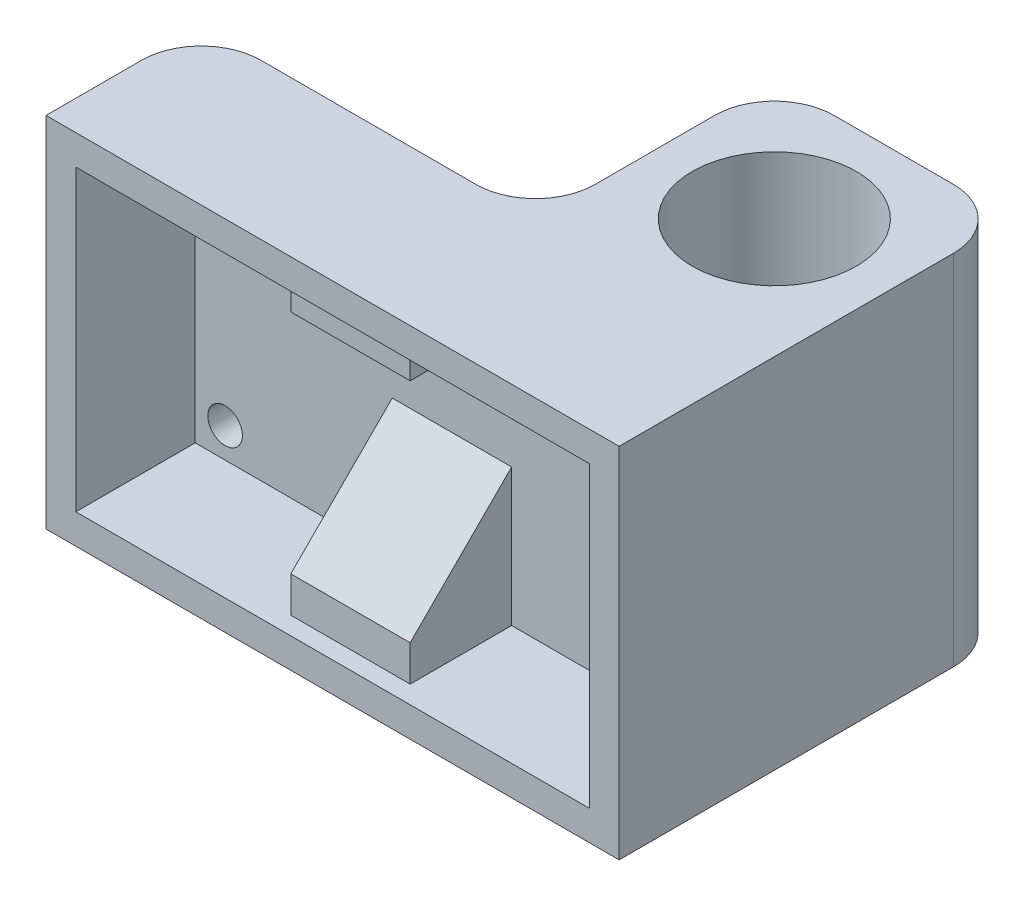
SolidWorks part; units mm, degrees
ref_plane "Front Plane" through (0, 0, 0) normal (0, 0, 1) x (1, 0, 0)
ref_plane "Top Plane" through (0, 0, 0) normal (0, 1, 0) x (1, 0, 0)
ref_plane "Right Plane" through (0, 0, 0) normal (1, 0, 0) x (0, 0, -1)
sketch "Sketch1" plane through (0, 0, 0) normal (0, 0, 1) x (1, 0, 0)
  line L0 (-0.5, 24.5) -> (16, 24.5)
  line L1 (0, 0) -> (42, 0) construction
  line L2 (0, 0) -> (0, 24) construction
  line L3 (0, 24) -> (42, 24) construction
  line L4 (42, 0) -> (42, 24) construction
  line L5 (-3, 27) -> (45, 27)
  line L6 (-3, 27) -> (-3, -3)
  line L7 (-3, -3) -> (45, -3)
  line L8 (45, 27) -> (45, -3)
  line L9 (42.5, 24.5) -> (42.5, -0.5)
  line L10 (-0.5, -0.5) -> (16, -0.5)
  line L11 (-0.5, 24.5) -> (-0.5, -0.5)
  line L12 (26, 24.5) -> (42.5, 24.5)
  line L14 (16, 24.5) -> (16, 21.5)
  line L15 (16, 21.5) -> (26, 21.5)
  line L16 (26, 24.5) -> (26, 21.5)
  line L18 (16, -0.5) -> (16, 2.5)
  line L19 (16, 2.5) -> (26, 2.5)
  line L20 (26, -0.5) -> (26, 2.5)
  line L21 (-0.5, 24.5) -> (42.5, 24.5) construction
  line L22 (26, -0.5) -> (42.5, -0.5)
  line L23 (-0.5, -0.5) -> (42.5, -0.5) construction
  circle A0 centre (2, 22) radius 1.625 construction
  circle A1 centre (2, 2) radius 1.625 construction
  circle A2 centre (40, 22) radius 1.625 construction
  circle A3 centre (40, 2) radius 1.625 construction
  point P29 (21, 27)
  point P30 (21, 21.5)
  point P31 (21, 2.5)
  dimension "D3" = 3.25
  dimension "D1" = 42
  dimension "D2" = 24
  dimension "D4" = 2
  dimension "D5" = 2
  dimension "D6" = 2
  dimension "D7" = 2
  dimension "D8" = 3
  dimension "D9" = 3
  dimension "D10" = 3
  dimension "D11" = 3
  dimension "D13" = 3
  dimension "D14" = 10
  dimension "D12" = 2.5
extrude "Boss-Extrude1" add sketch "Sketch1" along normal blind 10
sketch "Sketch2" plane through (0, 0, 10) normal (0, 0, 1) x (1, 0, 0)
  line L1 (16, -0.5) -> (26, -0.5)
  line L2 (16, -0.5) -> (16, 2.5)
  line L3 (16, 2.5) -> (26, 2.5)
  line L4 (26, -0.5) -> (26, 2.5)
  line L5 (16, 21.5) -> (26, 21.5)
  line L6 (16, 21.5) -> (16, 24.5)
  line L7 (16, 24.5) -> (26, 24.5)
  line L8 (26, 21.5) -> (26, 24.5)
extrude "Cut-Extrude1" cut sketch "Sketch2" against normal blind 1.5
sketch "Sketch3" plane through (0, 0, 0) normal (0, 0, -1) x (-1, 0, 0)
  line L1 (-45, 27) -> (3, 27)
  line L2 (-45, 27) -> (-45, -3)
  line L3 (-45, -3) -> (3, -3)
  line L4 (3, 27) -> (3, -3)
  circle A0 centre (-40, 22) radius 1.45
  circle A1 centre (-40, 2) radius 1.45
  circle A2 centre (-2, 22) radius 1.45
  circle A3 centre (-2, 2) radius 1.45
  dimension "D1" = 2.9
extrude "Boss-Extrude2" add sketch "Sketch3" along normal blind 3
sketch "Sketch4" plane through (0, 0, -3) normal (0, 0, -1) x (-1, 0, 0)
  line L0 (3, -3) -> (-45, -3) construction
  line L1 (-45, 27) -> (-25, 27)
  line L2 (-45, 27) -> (-45, -3)
  line L3 (-45, -3) -> (-25, -3)
  line L4 (-25, 27) -> (-25, -3)
  circle A0 centre (-40, 22) radius 1.45
  circle A1 centre (-40, 2) radius 1.45
  dimension "D1" = 20
extrude "Boss-Extrude3" add sketch "Sketch4" along normal blind 20
sketch "Sketch5" plane through (0, 27, 0) normal (0, 1, 0) x (1, 0, 0)
  line L0 (25, 23) -> (45, 23) construction
  line L1 (25, 23) -> (25, 3) construction
  circle A0 centre (35, 13) radius 6.875
  point P4 (35, 23)
  point P7 (25, 13)
  dimension "D1" = 13.75
extrude "Cut-Extrude2" cut sketch "Sketch5" against normal blind 35
fillet "Fillet1" radius 5 4 edges at (-3, 12, -3) (25, 12, -3) (45, 12, -23) (25, 12, -23)
chamfer "Chamfer1" distance 8.5 angle 45 1 edges at (21, 2.5, 0)
